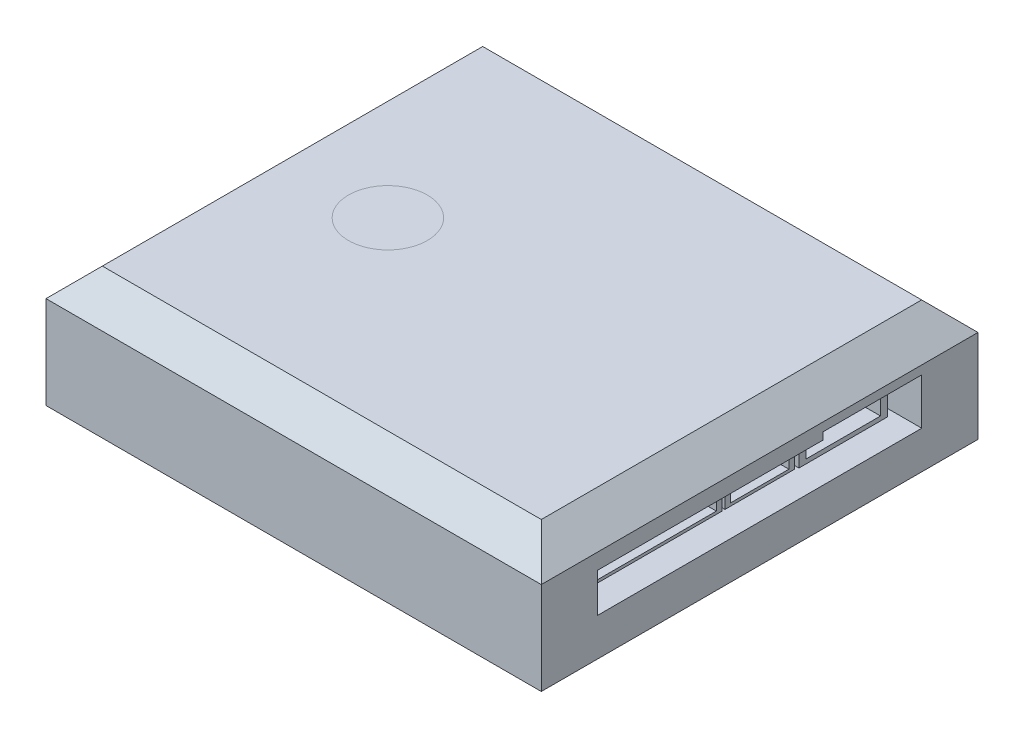
SolidWorks part; units mm, degrees
ref_plane "Front" through (0, 0, 0) normal (0, 0, 1) x (1, 0, 0)
ref_plane "Top" through (0, 0, 0) normal (0, 1, 0) x (1, 0, 0)
ref_plane "Right" through (0, 0, 0) normal (1, 0, 0) x (0, 0, -1)
sketch "Sketch1" plane through (0, 0, 0) normal (0, 1, 0) x (1, 0, 0)
  line L1 (-21.975, -19.375) -> (21.975, -19.375)
  line L2 (-21.975, -19.375) -> (-21.975, 19.375)
  line L3 (-21.975, 19.375) -> (21.975, 19.375)
  line L4 (21.975, -19.375) -> (21.975, 19.375)
  line L5 (-21.975, -19.375) -> (21.975, 19.375) construction
  line L6 (-21.975, 19.375) -> (21.975, -19.375) construction
  point P0 (0, 0)
  dimension "D1" = 43.95
  dimension "D2" = 38.75
extrude "Boss-Extrude1" add sketch "Sketch1" along normal blind 12.4968
chamfer "Chamfer1" distance 2.5 angle 45 4 edges at (0, 12.4968, 19.375) (-21.975, 12.4968, 0) (0, 12.4968, -19.375) (21.975, 12.4968, 0)
chamfer "Chamfer2" distance 1.778 angle 45 4 edges at (0, 0, -19.375) (-21.975, 0, 0) (0, 0, 19.375) (21.975, 0, 0)
sketch "Sketch2" plane through (21.975, 0, 0) normal (1, 0, 0) x (0, 0, -1)
  line L0 (19.375, 9.9968) -> (-19.375, 9.9968) construction
  line L1 (-14.3828, 8.5998) -> (14.3827, 8.5998)
  line L2 (-14.3828, 8.5998) -> (-14.3828, 5.1327)
  line L3 (-14.3828, 5.1327) -> (14.3827, 5.1327)
  line L4 (14.3827, 8.5998) -> (14.3827, 5.1327)
  line L5 (-14.3828, 8.5998) -> (14.3827, 5.1327) construction
  line L6 (-14.3828, 5.1327) -> (14.3827, 8.5998) construction
  line L7 (5.6197, 8.5998) -> (14.3827, 8.5998)
  line L8 (5.6197, 8.5998) -> (5.6197, 9.2348)
  line L9 (5.6197, 9.2348) -> (14.3827, 9.2348)
  line L10 (14.3827, 8.5998) -> (14.3827, 9.2348)
  point P0 (0, 6.8663)
  point P5 (14.3827, 8.9173)
  point P11 (14.3827, 6.8663)
  dimension "D1" = 28.7655
  dimension "D2" = 3.4671
  dimension "D3" = 4.1021
  dimension "D4" = 8.763
  dimension "D5" = 0.762
extrude "Cut-Extrude1" cut sketch "Sketch2" against normal blind 6.9342 contours L4 L1 L2 L3 | L1 L10 L9 L8 region at (21.975, 6.8663, 0) region at (21.975, 8.9173, -10.0012)
sketch "Sketch3" plane through (15.0408, 0, 0) normal (1, 0, 0) x (0, 0, -1)
  line L0 (-14.3828, 8.5998) -> (-14.3828, 5.1327) construction
  line L1 (-13.6208, 8.3712) -> (-1.0732, 8.3712)
  line L2 (-13.6208, 8.3712) -> (-13.6208, 5.3613)
  line L3 (-13.6208, 5.3613) -> (-1.0732, 5.3613)
  line L4 (-1.0732, 8.3712) -> (-1.0732, 5.3613)
  line L5 (5.6197, 8.5998) -> (5.6197, 9.2348) construction
  line L6 (5.7467, 9.1078) -> (13.6207, 9.1078)
  line L7 (5.7467, 9.1078) -> (5.7467, 5.2597)
  line L8 (5.7467, 5.2597) -> (13.6207, 5.2597)
  line L9 (13.6207, 9.1078) -> (13.6207, 5.2597)
  line L10 (14.3827, 9.2348) -> (14.3827, 5.1327) construction
  line L11 (5.6197, 9.2348) -> (14.3827, 9.2348) construction
  line L12 (-14.3828, 5.1327) -> (14.3827, 5.1327) construction
  line L13 (-7.347, 8.1172) -> (-7.347, 5.6153) construction
  line L14 (-0.8192, 8.3712) -> (5.3657, 8.3712)
  line L15 (-0.8192, 8.3712) -> (-0.8192, 5.3613)
  line L16 (-0.8192, 5.3613) -> (5.3657, 5.3613)
  line L17 (5.3657, 8.3712) -> (5.3657, 5.3613)
  line L18 (-13.1128, 8.1172) -> (-1.5812, 8.1172)
  line L19 (-13.1128, 8.1172) -> (-13.1128, 7.6092)
  line L20 (-13.1128, 5.6153) -> (-1.5812, 5.6153)
  line L21 (-1.5812, 8.1172) -> (-1.5812, 7.6092)
  line L22 (-13.1128, 7.1012) -> (-13.3668, 7.1012)
  line L23 (-1.5812, 7.1012) -> (-1.5812, 5.6153)
  line L24 (-13.1128, 7.6092) -> (-13.3668, 7.6092)
  line L25 (-13.3668, 7.1012) -> (-13.3668, 7.6092)
  line L26 (-1.3272, 7.1012) -> (-1.3272, 7.6092)
  line L27 (-1.5812, 7.6092) -> (-1.3272, 7.6092)
  line L28 (2.2733, 8.1172) -> (2.2733, 5.6153) construction
  line L29 (-1.5812, 7.1012) -> (-1.3272, 7.1012)
  line L30 (-13.1128, 7.1012) -> (-13.1128, 5.6153)
  line L31 (-0.3112, 8.1172) -> (4.8577, 8.1172)
  line L32 (-0.3112, 8.1172) -> (-0.3112, 7.6092)
  line L33 (-0.3112, 5.6153) -> (4.8577, 5.6153)
  line L34 (4.8577, 8.1172) -> (4.8577, 7.6092)
  line L35 (-0.3112, 7.1012) -> (-0.5652, 7.1012)
  line L36 (4.8577, 7.1012) -> (4.8577, 5.6153)
  line L37 (-0.3112, 7.6092) -> (-0.5652, 7.6092)
  line L38 (-0.5652, 7.1012) -> (-0.5652, 7.6092)
  line L39 (5.1117, 7.1012) -> (5.1117, 7.6092)
  line L40 (4.8577, 7.6092) -> (5.1117, 7.6092)
  line L41 (9.6837, 8.7268) -> (9.6837, 5.6407) construction
  line L42 (4.8577, 7.1012) -> (5.1117, 7.1012)
  line L43 (-0.3112, 7.1012) -> (-0.3112, 5.6153)
  line L44 (6.3817, 8.7268) -> (12.9857, 8.7268)
  line L45 (6.3817, 8.7268) -> (6.3817, 8.2188)
  line L46 (6.3817, 5.6407) -> (12.9857, 5.6407)
  line L47 (12.9857, 8.7268) -> (12.9857, 8.2188)
  line L48 (6.3817, 7.4568) -> (6.0007, 7.4568)
  line L49 (12.9857, 7.4568) -> (12.9857, 5.6407)
  line L50 (6.3817, 8.2188) -> (6.0007, 8.2188)
  line L51 (6.0007, 7.4568) -> (6.0007, 8.2188)
  line L52 (13.3667, 7.4568) -> (13.3667, 8.2188)
  line L53 (12.9857, 8.2188) -> (13.3667, 8.2188)
  line L55 (12.9857, 7.4568) -> (13.3667, 7.4568)
  line L56 (6.3817, 7.4568) -> (6.3817, 5.6407)
  point P4 (-13.6208, 6.8663)
  point P7 (-14.3828, 6.8663)
  point P14 (5.6197, 8.9173)
  dimension "D1" = 0.762
  dimension "D2" = 12.5476
  dimension "D3" = 3.0099
  dimension "D4" = 0.127
  dimension "D5" = 0.762
  dimension "D6" = 0.127
  dimension "D7" = 0.127
  dimension "D8" = 0.254
  dimension "D9" = 0.254
  dimension "D10" = 0.254
  dimension "D11" = 0.254
  dimension "D12" = 0.508
  dimension "D13" = 0.508
  dimension "D14" = 0.508
  dimension "D15" = 0.508
  dimension "D16" = 0.254
  dimension "D17" = 0.508
  dimension "D18" = 0.508
  dimension "D19" = 0.254
  dimension "D20" = 0.381
  dimension "D21" = 0.381
  dimension "D22" = 0.635
  dimension "D23" = 0.635
  dimension "D24" = 0.381
  dimension "D25" = 0.762
  dimension "D26" = 0.508
extrude "Boss-Extrude2" add sketch "Sketch3" along normal offset from surface (4.6736 mm away) 2.2606 contours L22 L30 L20 L23 L29 L26 L27 L21 L18 L19 L24 L25 | L35 L43 L33 L36 L42 L39 L40 L34 L31 L32 L37 L38 | L48 L56 L46 L49 L55 L52 L53 L47 L44 L45 L50 L51 | L4 L1 L2 L3 L30 L22 L25 L24 L19 L18 L21 L27 L26 L29 L23 L20 | L17 L14 L15 L16 L43 L35 L38 L37 L32 L31 L34 L40 L39 L42 L36 L33 | L9 L6 L7 L8 L56 L48 L51 L50 L45 L44 L47 L53 L52 L55 L49 L46 region at (15.0408, 8.2422, 7.347) region at (15.0408, 9.0202, -9.6837) region at (15.0408, 8.3024, -2.2733) region at (15.0408, 6.8706, 7.347) region at (15.0408, 6.8758, -2.2733) region at (15.0408, 7.2019, -9.6837) up to face at (21.975, 5.8874, 0)
extrude "Cut-Extrude3" cut sketch "Sketch3<4>" along normal up to surface (4.6736 mm away) from offset 1.27 contours L22 L30 L20 L23 L29 L26 L27 L21 L18 L19 L24 L25 | L35 L43 L33 L36 L42 L39 L40 L34 L31 L32 L37 L38 | L48 L56 L46 L49 L55 L52 L53 L47 L44 L45 L50 L51 region at (15.0408, 6.8706, 7.347) region at (15.0408, 6.8758, -2.2733) region at (15.0408, 7.2019, -9.6837) up to face at (19.7144, 6.8663, 7.347)
sketch "Sketch3<4>" plane through (15.0408, 0, 0) normal (1, 0, 0) x (0, 0, -1) same geometry as "Sketch3"
sketch "Sketch4" plane through (16.3108, 0, 0) normal (1, 0, 0) x (0, 0, -1)
  line L0 (-13.3668, 7.3552) -> (-1.3272, 7.3552) construction
  line L1 (-13.3668, 7.6092) -> (-13.3668, 7.1012) construction
  line L2 (-1.3272, 7.6092) -> (-1.3272, 7.1012) construction
  line L3 (-0.5652, 7.3552) -> (5.1117, 7.3552) construction
  line L4 (-0.5652, 7.6092) -> (-0.5652, 7.1012) construction
  line L5 (5.1117, 7.6092) -> (5.1117, 7.1012) construction
  line L6 (6.0007, 7.8378) -> (13.3667, 7.8378) construction
  line L7 (6.0007, 7.4568) -> (6.0007, 8.2188) construction
  line L8 (13.3667, 7.4568) -> (13.3667, 8.2188) construction
  circle A0 centre (-12.6299, 7.3552) radius 0.1905
  circle A1 centre (-11.4615, 7.3552) radius 0.1905
  circle A2 centre (-10.2931, 7.3552) radius 0.1905
  circle A3 centre (-9.1247, 7.3552) radius 0.1905
  circle A4 centre (-7.9563, 7.3552) radius 0.1905
  circle A5 centre (-6.7879, 7.3552) radius 0.1905
  circle A6 centre (-5.6195, 7.3552) radius 0.1905
  circle A7 centre (-4.4511, 7.3552) radius 0.1905
  circle A8 centre (-3.2827, 7.3552) radius 0.1905
  circle A9 centre (-2.1143, 7.3552) radius 0.1905
  circle A10 centre (0.343, 7.3552) radius 0.1905
  circle A11 centre (2.248, 7.3552) radius 0.1905
  circle A12 centre (4.153, 7.3552) radius 0.1905
  circle A13 centre (7.146, 7.8378) radius 0.254
  circle A14 centre (9.686, 7.8378) radius 0.254
  circle A15 centre (12.226, 7.8378) radius 0.254
  dimension "D1" = 0.381
  dimension "D3" = 1.1684
  dimension "D4" = 0.381
  dimension "D6" = 0.508
  dimension "D8" = 1.905
  dimension "D2" = 10
  dimension "D5" = 3
  dimension "D7" = 3
extrude "Pins" add sketch "Sketch4" along normal blind 3.0226
sketch "Sketch5" plane through (0, 12.4968, 0) normal (0, 1, 0) x (1, 0, 0)
  line L0 (0, 0) -> (-17.7525, -0.8354) construction
  circle A0 centre (-10.5173, -0.4949) radius 3.5
  dimension "D1" = 7
split line "LED"
sketch "Sketch6" plane through (0, 0, -19.375) normal (0, 0, -1) x (-1, 0, 0)
  line L0 (62.7526, 70.2944) -> (222.4815, 70.2944) construction
  line L1 (4.577, 8.7842) -> (4.577, 6.3643) construction
  line L2 (2.595, 7.7857) -> (2.341, 7.7857)
  line L3 (8.3371, 7.7857) -> (8.3371, 6.3643)
  line L4 (3.2162, 5.8563) -> (5.5914, 5.8563)
  line L5 (2.595, 8.2937) -> (2.341, 8.2937)
  line L6 (2.595, 8.7842) -> (6.5591, 8.7842)
  line L7 (2.595, 8.7842) -> (2.595, 8.2937)
  line L8 (2.341, 7.7857) -> (2.341, 8.2937)
  line L9 (10.9231, 8.7842) -> (10.9231, 6.3643) construction
  line L11 (5.5914, 5.8563) -> (14.7792, 5.8563)
  line L12 (1.579, 9.2922) -> (14.7792, 9.2922)
  line L13 (1.579, 9.2922) -> (1.579, 5.8563)
  line L14 (1.579, 5.8563) -> (3.2162, 5.8563)
  line L15 (14.7792, 9.2922) -> (14.7792, 5.8563)
  line L16 (2.595, 6.3643) -> (6.5591, 6.3643)
  line L17 (6.5591, 8.7842) -> (6.5591, 8.2937)
  line L18 (8.3371, 8.7842) -> (13.5092, 8.7842)
  line L19 (8.3371, 8.7842) -> (8.3371, 8.2937)
  line L20 (2.087, 9.0382) -> (7.0671, 9.0382)
  line L21 (2.087, 9.0382) -> (2.087, 6.1103)
  line L22 (2.087, 6.1103) -> (7.0671, 6.1103)
  line L23 (7.0671, 9.0382) -> (7.0671, 6.1103)
  line L24 (7.8291, 9.0382) -> (14.0172, 9.0382)
  line L25 (7.8291, 9.0382) -> (7.8291, 6.1103)
  line L26 (7.8291, 6.1103) -> (14.0172, 6.1103)
  line L27 (14.0172, 9.0382) -> (14.0172, 6.1103)
  line L28 (8.3371, 6.3643) -> (13.5092, 6.3643)
  line L29 (13.5092, 8.7842) -> (13.5092, 8.2937)
  line L30 (8.3371, 7.7857) -> (8.0831, 7.7857)
  line L31 (13.5092, 7.7857) -> (13.5092, 6.3643)
  line L32 (8.3371, 8.2937) -> (8.0831, 8.2937)
  line L33 (8.0831, 7.7857) -> (8.0831, 8.2937)
  line L34 (6.8131, 7.7857) -> (6.8131, 8.2937)
  line L35 (6.5591, 8.2937) -> (6.8131, 8.2937)
  line L37 (6.5591, 7.7857) -> (6.8131, 7.7857)
  line L38 (13.7632, 7.7857) -> (13.7632, 8.2937)
  line L39 (13.5092, 8.2937) -> (13.7632, 8.2937)
  line L41 (13.5092, 7.7857) -> (13.7632, 7.7857)
  line L42 (2.595, 7.7857) -> (2.595, 6.3643)
  line L43 (6.5591, 7.7857) -> (6.5591, 6.3643)
  point P10 (2.087, 7.5743)
  point P30 (14.0172, 7.5743)
  point P31 (14.7792, 7.5743)
  dimension "D1" = 0.254
  dimension "D2" = 0.254
  dimension "D3" = 0.254
  dimension "D4" = 0.254
  dimension "D5" = 0.762
  dimension "D6" = 0.762
  dimension "D7" = 0.508
  dimension "D8" = 0.254
  dimension "D9" = 0.254
  dimension "D10" = 0.508
  dimension "D11" = 0.508
  dimension "D12" = 0.508
  dimension "D13" = 0.508
  dimension "D14" = 0.254
  dimension "D15" = 0.508
  dimension "D16" = 0.254
extrude "Cut-Extrude4" cut sketch "Sketch6" against normal blind 7.366 contours L15 L12 L13 L14 L4 L11 L20 L23 L22 L21 L24 L27 L26 L25 | L43 L37 L34 L35 L17 L6 L7 L5 L8 L2 L42 L16 | L31 L41 L38 L39 L29 L18 L19 L32 L33 L30 L3 L28 | L23 L20 L21 L22 L37 L43 L16 L42 L2 L8 L5 L7 L6 L17 L35 L34 | L27 L24 L25 L26 L41 L31 L28 L3 L30 L33 L32 L19 L18 L29 L39 L38 region at (-4.577, 7.5865, -19.375) region at (-10.9231, 7.5837, -19.375) region at (-2.3976, 5.9927, -19.375) region at (-4.577, 8.9805, -19.375) region at (-10.9231, 8.9698, -19.375)
extrude "Boss-Extrude6" add sketch "Sketch6<7>" against normal blind 7.366 from offset 2.286 contours L23 L20 L21 L22 L37 L43 L16 L42 L2 L8 L5 L7 L6 L17 L35 L34 | L27 L24 L25 L26 L41 L31 L28 L3 L30 L33 L32 L19 L18 L29 L39 L38 region at (-4.577, 8.9805, -19.375) region at (-10.9231, 8.9698, -19.375) offset against normal yes
sketch "Sketch6<7>" plane through (0, 0, -19.375) normal (0, 0, -1) x (-1, 0, 0) same geometry as "Sketch6"
extrude "Boss-Extrude7" add sketch "Sketch6<8>" along normal blind 1.27 from offset 5.08 contours L43 L37 L34 L35 L17 L6 L7 L5 L8 L2 L42 L16 | L31 L41 L38 L39 L29 L18 L19 L32 L33 L30 L3 L28 region at (-4.577, 7.5865, -19.375) region at (-10.9231, 7.5837, -19.375) offset against normal yes
sketch "Sketch6<8>" plane through (0, 0, -19.375) normal (0, 0, -1) x (-1, 0, 0) same geometry as "Sketch6"
sketch "Sketch7" plane through (0, 0, -15.565) normal (0, 0, -1) x (-1, 0, 0)
  line L0 (2.341, 8.0397) -> (6.8131, 8.0397) construction
  line L1 (2.341, 7.7857) -> (2.341, 8.2937) construction
  line L2 (6.8131, 7.7857) -> (6.8131, 8.2937) construction
  line L3 (8.0831, 8.0397) -> (13.7632, 8.0397) construction
  line L4 (8.0831, 7.7857) -> (8.0831, 8.2937) construction
  line L5 (13.7632, 7.7857) -> (13.7632, 8.2937) construction
  circle A0 centre (3.2393, 8.0397) radius 0.1905
  circle A1 centre (8.9588, 8.0397) radius 0.1905
  circle A2 centre (4.5093, 8.0397) radius 0.1905
  circle A3 centre (5.7793, 8.0397) radius 0.1905
  circle A4 centre (10.2288, 8.0397) radius 0.1905
  circle A5 centre (11.4988, 8.0397) radius 0.1905
  circle A6 centre (12.7688, 8.0397) radius 0.1905
  dimension "D1" = 0.381
  dimension "D2" = 0.381
  dimension "D3" = 3
  dimension "D4" = 4
extrude "Boss-Extrude8" add sketch "Sketch7" along normal blind 1.524
sketch "Sketch8" plane through (-21.975, 0, 0) normal (-1, 0, 0) x (0, 0, 1)
  line L0 (494.9714, 1194.3432) -> (2000.69, 1194.3432) construction
  line L1 (-19.375, 0) -> (19.4341, 0)
  line L2 (-19.375, 0) -> (-19.375, 12.5052)
  line L3 (-19.375, 12.5052) -> (19.4341, 12.5052)
  line L4 (19.4341, 0) -> (19.4341, 12.5052)
  line L5 (-8.9037, 8.4372) -> (-8.9037, 5.9082) construction
  line L6 (-13.8236, 9.4532) -> (13.8738, 9.4532)
  line L7 (-13.8236, 9.4532) -> (-13.8236, 5.1462)
  line L8 (-13.8236, 5.1462) -> (13.8738, 5.1462)
  line L9 (13.8738, 9.4532) -> (13.8738, 5.1462)
  line L10 (-13.0616, 8.6912) -> (-4.7458, 8.6912)
  line L11 (-13.0616, 8.6912) -> (-13.0616, 5.6542)
  line L12 (-13.0616, 5.6542) -> (-4.7458, 5.6542)
  line L13 (-4.7458, 8.6912) -> (-4.7458, 5.6542)
  line L14 (-3.2218, 8.6912) -> (2.9406, 8.6912)
  line L15 (-3.2218, 8.6912) -> (-3.2218, 5.6542)
  line L16 (-3.2218, 5.6542) -> (2.9406, 5.6542)
  line L17 (2.9406, 8.6912) -> (2.9406, 5.6542)
  line L18 (4.4646, 8.6912) -> (13.1118, 8.6912)
  line L19 (4.4646, 8.6912) -> (4.4646, 5.6542)
  line L20 (4.4646, 5.6542) -> (13.1118, 5.6542)
  line L21 (13.1118, 8.6912) -> (13.1118, 5.6542)
  line L22 (-12.5536, 8.4372) -> (-5.2538, 8.4372)
  line L23 (-12.5536, 8.4372) -> (-12.5536, 7.9417)
  line L24 (-12.5536, 5.9082) -> (-5.2538, 5.9082)
  line L25 (-5.2538, 8.4372) -> (-5.2538, 7.9417)
  line L26 (-2.7138, 8.4372) -> (2.4326, 8.4372)
  line L27 (-2.7138, 8.4372) -> (-2.7138, 7.9417)
  line L28 (-2.7138, 5.9082) -> (2.4326, 5.9082)
  line L29 (2.4326, 8.4372) -> (2.4326, 7.9417)
  line L30 (4.9726, 8.4372) -> (12.6038, 8.4372)
  line L31 (4.9726, 8.4372) -> (4.9726, 7.9417)
  line L32 (4.9726, 5.9082) -> (12.6038, 5.9082)
  line L33 (12.6038, 8.4372) -> (12.6038, 7.9417)
  line L34 (-12.5536, 7.4337) -> (-12.8076, 7.4337)
  line L35 (-5.2538, 7.4337) -> (-5.2538, 5.9082)
  line L36 (-12.5536, 7.9417) -> (-12.8076, 7.9417)
  line L37 (-12.8076, 7.4337) -> (-12.8076, 7.9417)
  line L38 (-0.1406, 8.4372) -> (-0.1406, 5.9082) construction
  line L39 (8.7882, 8.4372) -> (8.7882, 5.9082) construction
  line L41 (-2.7138, 7.9417) -> (-2.9678, 7.9417)
  line L42 (2.4326, 7.4337) -> (2.4326, 5.9082)
  line L43 (-2.7138, 7.4337) -> (-2.9678, 7.4337)
  line L44 (-2.9678, 7.9417) -> (-2.9678, 7.4337)
  line L45 (-4.9998, 7.4337) -> (-4.9998, 7.9417)
  line L46 (4.9726, 7.4337) -> (4.7186, 7.4337)
  line L47 (12.6038, 7.4337) -> (12.6038, 5.9082)
  line L48 (4.9726, 7.9417) -> (4.7186, 7.9417)
  line L49 (4.7186, 7.4337) -> (4.7186, 7.9417)
  line L50 (-5.2538, 7.9417) -> (-4.9998, 7.9417)
  line L51 (-2.7138, 7.4337) -> (-2.7138, 5.9082)
  line L52 (-5.2538, 7.4337) -> (-4.9998, 7.4337)
  line L53 (2.6866, 7.9417) -> (2.6866, 7.4337)
  line L54 (2.4326, 7.4337) -> (2.6866, 7.4337)
  line L55 (4.9726, 7.4337) -> (4.9726, 5.9082)
  line L56 (2.4326, 7.9417) -> (2.6866, 7.9417)
  line L57 (12.8578, 7.4337) -> (12.8578, 7.9417)
  line L58 (12.6038, 7.9417) -> (12.8578, 7.9417)
  line L60 (12.6038, 7.4337) -> (12.8578, 7.4337)
  line L61 (-12.5536, 7.4337) -> (-12.5536, 5.9082)
  point P34 (-3.2218, 7.1727)
  dimension "D1" = 0.762
  dimension "D2" = 0.762
  dimension "D3" = 1.524
  dimension "D4" = 1.524
  dimension "D5" = 0.508
  dimension "D6" = 0.762
  dimension "D7" = 10.6019
  dimension "D8" = 6.1624
  dimension "D9" = 0.254
  dimension "D10" = 0.254
  dimension "D11" = 0.508
  dimension "D12" = 0.508
  dimension "D13" = 0.508
  dimension "D14" = 0.508
  dimension "D15" = 0.508
  dimension "D16" = 0.508
  dimension "D17" = 0.254
  dimension "D18" = 0.508
  dimension "D19" = 0.254
  dimension "D20" = 0.254
extrude "Cut-Extrude5" cut sketch "Sketch8" against normal offset from surface (7.1704 mm away) 0.0254 contours L9 L6 L7 L8 L10 L13 L12 L11 L14 L17 L16 L15 L18 L21 L20 L19 | L13 L10 L11 L12 L61 L34 L37 L36 L23 L22 L25 L50 L45 L52 L35 L24 | L34 L61 L24 L35 L52 L45 L50 L25 L22 L23 L36 L37 | L17 L14 L15 L16 L29 L56 L53 L54 L42 L28 L51 L43 L44 L41 L27 L26 | L56 L29 L26 L27 L41 L44 L43 L51 L28 L42 L54 L53 | L21 L18 L19 L20 L60 L47 L32 L55 L46 L49 L48 L31 L30 L33 L58 L57 | L47 L60 L57 L58 L33 L30 L31 L48 L49 L46 L55 L32 region at (-21.975, 9.1729, 0.0251) region at (-21.975, 8.6027, -8.9037) region at (-21.975, 8.6225, -0.1406) region at (-21.975, 8.5996, 8.7882) region at (-21.975, 7.1798, -8.9037) region at (-21.975, 7.1827, -0.1406) region at (-21.975, 7.1795, 8.7882) up to face at (-14.7792, 7.5743, -15.692)
extrude "Boss-Extrude9" add sketch "Sketch8<3>" against normal up to surface (7.1704 mm away) from offset 2.286 contours L13 L10 L11 L12 L61 L34 L37 L36 L23 L22 L25 L50 L45 L52 L35 L24 | L17 L14 L15 L16 L29 L56 L53 L54 L42 L28 L51 L43 L44 L41 L27 L26 | L21 L18 L19 L20 L60 L47 L32 L55 L46 L49 L48 L31 L30 L33 L58 L57 region at (-21.975, 8.6027, -8.9037) region at (-21.975, 8.6225, -0.1406) region at (-21.975, 8.5996, 8.7882) up to face at (-14.8046, 7.2997, 0.0251) offset against normal yes
sketch "Sketch8<3>" plane through (-21.975, 0, 0) normal (-1, 0, 0) x (0, 0, 1) same geometry as "Sketch8"
extrude "Boss-Extrude10" add sketch "Sketch8<5>" along normal blind 1.27 from offset 7.112 contours L34 L61 L24 L35 L52 L45 L50 L25 L22 L23 L36 L37 | L56 L29 L26 L27 L41 L44 L43 L51 L28 L42 L54 L53 | L47 L60 L57 L58 L33 L30 L31 L48 L49 L46 L55 L32 region at (-21.975, 7.1798, -8.9037) region at (-21.975, 7.1827, -0.1406) region at (-21.975, 7.1795, 8.7882) offset against normal yes
sketch "Sketch8<5>" plane through (-21.975, 0, 0) normal (-1, 0, 0) x (0, 0, 1) same geometry as "Sketch8"
sketch "Sketch9" plane through (-16.133, 0, 0) normal (-1, 0, 0) x (0, 0, 1)
  line L0 (-12.8076, 7.6877) -> (12.8578, 7.6877) construction
  line L1 (-12.8076, 7.4337) -> (-12.8076, 7.9417) construction
  line L2 (12.8578, 7.4337) -> (12.8578, 7.9417) construction
  circle A0 centre (-12.0997, 7.6877) radius 0.1905
  circle A1 centre (-2.0834, 7.6877) radius 0.1905
  circle A2 centre (5.583, 7.6877) radius 0.1905
  circle A3 centre (-10.8297, 7.6877) radius 0.1905
  circle A4 centre (-9.5597, 7.6877) radius 0.1905
  circle A5 centre (-8.2897, 7.6877) radius 0.1905
  circle A6 centre (-7.0197, 7.6877) radius 0.1905
  circle A7 centre (-5.7497, 7.6877) radius 0.1905
  circle A8 centre (6.853, 7.6877) radius 0.1905
  circle A9 centre (8.123, 7.6877) radius 0.1905
  circle A10 centre (9.393, 7.6877) radius 0.1905
  circle A11 centre (10.663, 7.6877) radius 0.1905
  circle A12 centre (11.933, 7.6877) radius 0.1905
  circle A13 centre (-0.8134, 7.6877) radius 0.1905
  circle A14 centre (0.4566, 7.6877) radius 0.1905
  circle A15 centre (1.7266, 7.6877) radius 0.1905
  dimension "D1" = 0.381
  dimension "D2" = 6
  dimension "D3" = 6
  dimension "D4" = 4
extrude "Boss-Extrude11" add sketch "Sketch9" along normal blind 3.302
